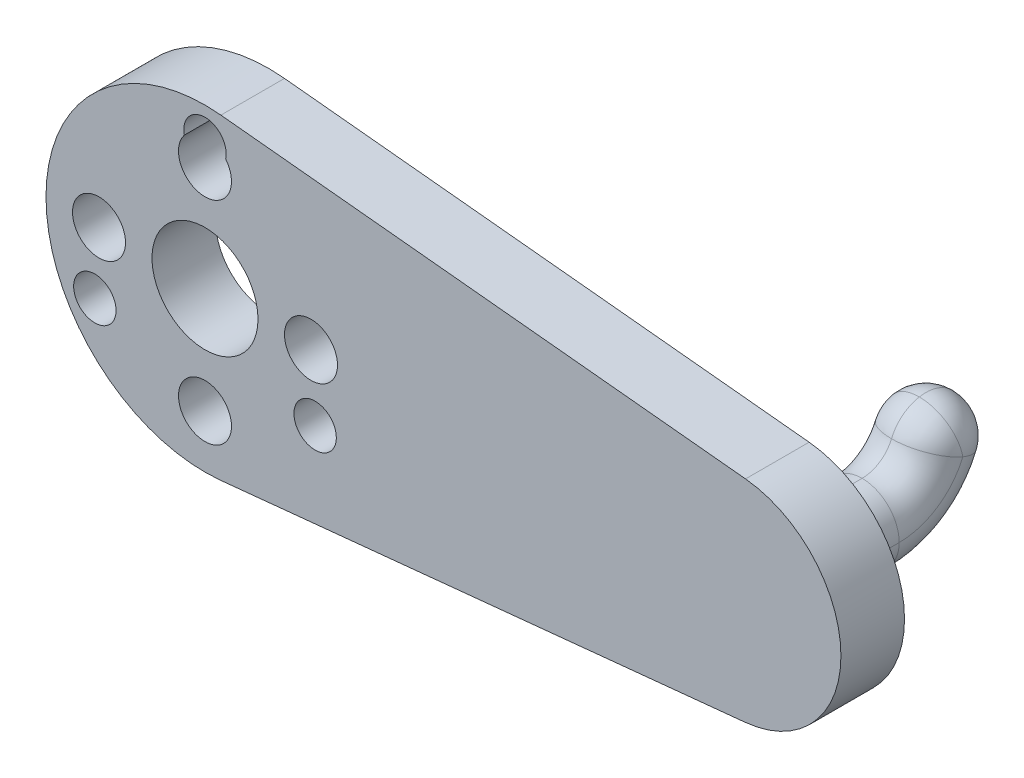
SolidWorks part; units mm, degrees
note: '?' marks a value the reader was unsure of.
ref_plane "前视基准面" through (0, 0, 0) normal (0, 0, 1) x (1, 0, 0)
ref_plane "上视基准面" through (0, 0, 0) normal (0, 1, 0) x (1, 0, 0)
ref_plane "右视基准面" through (0, 0, 0) normal (1, 0, 0) x (0, 0, -1)
other "Configuration Table"
sketch "草图1" plane through (0, 0, 0) normal (0, 0, 1) x (1, 0, 0)
  line L0 (0.75, 7.4624) -> (25.5, 4.9749)
  line L1 (-12.4707, 0) -> (35.367, 0) construction
  line L2 (0.75, -7.4624) -> (25.5, -4.9749)
  arc A0 (-0.9758, 5.7812) -> (0.9758, 5.7813) centre (0, 5) ccw
  circle A1 centre (5, 0) radius 1.25
  circle A2 centre (0, -5) radius 1.25
  circle A3 centre (-5, 0) radius 1.25
  circle A4 centre (0, 0) radius 2.5
  arc A5 (0.75, 7.4624) -> (0.75, -7.4624) centre (0, 0) ccw
  arc A6 (25.5, -4.9749) -> (25.5, 4.9749) centre (25, 0) ccw
  arc A7 (0.9758, 5.7813) -> (-0.9758, 5.7812) centre (0, 6) ccw
  circle A8 centre (5.1962, -3) radius 1
  circle A9 centre (-5.1962, -3) radius 1
  point P10 (0, 0)
  point P26 (0, 0)
  dimension "D1" = 2.5
  dimension "D2" = 5
  dimension "D3" = 15
  dimension "D4" = 5
  dimension "D5" = 25
  dimension "D6" = 2
extrude "凸台-拉伸1" add sketch "草图1" along normal blind 3
ref_axis "基准轴1" through (25, 0, 3) along (0, 0, -1)?
ref_plane "基准面1" through (25, 0, 0) normal (1, 0, 0) x (0, 0, -1)
sketch "草图2" plane through (25, 0, 0) normal (1, 0, 0) x (0, 0, -1)
  line L0 (-4.9151, 0) -> (8.5041, 0) construction
  line L1 (0, -4.9749) -> (0, 4.9749) construction
  line L2 (3, -1.75) -> (0, -1.75)
  line L4 (3, 1.75) -> (0, 1.75)
  line L5 (0, -1.75) -> (0, 1.75)
  line L6 (3, -1.75) -> (0, 1.75) construction
  line L7 (3, 1.75) -> (0, -1.75) construction
  line L8 (4.4772, 3.5105) -> (7.924, 4.1182)
  arc A0 (3, 1.75) -> (4.4772, 3.5105) centre (3, 3.25) ccw
  arc A1 (3, -1.75) -> (7.924, 4.1182) centre (3, 3.25) ccw
  point P3 (1.5, 0)
  dimension "D4" = 1.5
  dimension "D2" = 3.5
  dimension "D3" = 3
  dimension "D5" = 10
  dimension "D1" = 3.5
extrude "凸台-拉伸2" add sketch "草图2" along normal mid plane 3.5
fillet "圆角1" radius 1.75 8 edges at (23.25, -1.75, -1.5) (26.75, -1.75, -1.5) (23.25, 2.2858, -4.1491) (26.75, 1.75, -1.5) (23.25, 0.0361, -6.8302) (26.75, 0.0361, -6.8302) (23.25, 1.75, -1.5) (26.75, 2.2858, -4.1491)
